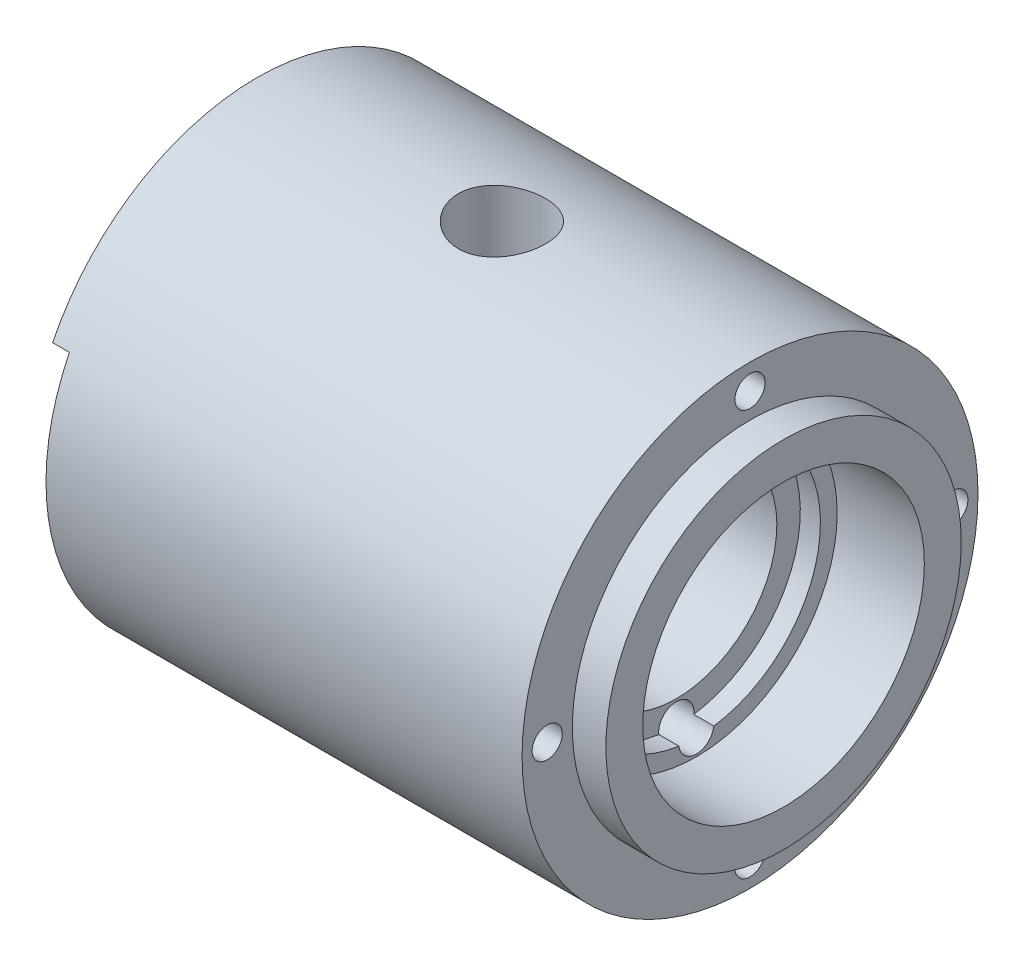
SolidWorks part; units mm, degrees
ref_plane "Front Plane" through (0, 0, 0) normal (0, 0, 1) x (1, 0, 0)
ref_plane "Top Plane" through (0, 0, 0) normal (0, 1, 0) x (1, 0, 0)
ref_plane "Right Plane" through (0, 0, 0) normal (1, 0, 0) x (0, 0, -1)
sketch "Sketch17" plane through (0, 0, 0) normal (0, 0, 1) x (1, 0, 0)
  line L0 (0, 0) -> (156.5215, 0) construction
sketch "Sketch1" plane through (0, 0, 0) normal (1, 0, 0) x (0, 0, -1)
  circle A0 centre (0, 0) radius 68
extrude "Boss-Extrude1" add sketch "Sketch1" along normal blind 157 contours A0
sketch "Sketch2" plane through (0, 0, 0) normal (-1, 0, 0) x (0, 0, 1)
  circle A0 centre (0, 0) radius 26
extrude "Cut-Extrude1" cut sketch "Sketch2" against normal up to next
sketch "Sketch3" plane through (0, 0, 0) normal (-1, 0, 0) x (0, 0, 1)
  line L1 (-68, 30) -> (68, 30)
  line L2 (-68, 30) -> (-68, -68)
  line L3 (-68, -68) -> (68, -68)
  line L4 (68, 30) -> (68, -68)
  circle A2 centre (0, 0) radius 68 construction
  circle A3 centre (0, 0) radius 26 construction
  dimension "D1" = 30
  dimension "D2" = 68
  dimension "D3" = 42
  dimension "D4" = 68
  dimension "D5" = 68
extrude "Cut-Extrude2" cut sketch "Sketch3" against normal blind 5 contours L2 L3 L4 L1
sketch "Sketch4" plane through (5, 0, 0) normal (-1, 0, 0) x (0, 0, 1)
  line L3 (-13.5, 29.0129) -> (13.5, 29.0129)
  arc A3 (-13.5, 29.0129) -> (13.5, 29.0129) centre (0, 0) ccw
  point P2 (-12.1706, 28.9683)
  point P3 (13.4809, 29.0218)
  point P5 (0, 0)
  point P6 (0, 0)
  point P7 (13.5, 28.9963)
  dimension "D1" = 27
extrude "Cut-Extrude3" cut sketch "Sketch4" against normal blind 44
sketch "Sketch7" plane through (157, 0, 0) normal (1, 0, 0) x (0, 0, -1)
  circle A0 centre (0, 0) radius 42
extrude "Cut-Extrude4" cut sketch "Sketch7" against normal blind 26
sketch "Sketch8" plane through (131, 0, 0) normal (1, 0, 0) x (0, 0, -1)
  circle A0 centre (0, 0) radius 37
extrude "Cut-Extrude5" cut sketch "Sketch8" against normal blind 6 contours A0
sketch "Sketch9" plane through (125, 0, 0) normal (1, 0, 0) x (0, 0, -1)
  circle A0 centre (0, 0) radius 30
extrude "Cut-Extrude6" cut sketch "Sketch9" against normal blind 28 contours A0
ref_plane "Plane2" through (0, 0, 68) normal (0, 0, 1) x (1, 0, 0)
sketch "Sketch12" plane through (0, 0, 68) normal (0, 0, 1) x (1, 0, 0)
  line L0 (49, 37.9633) -> (49, -31.4216)
  line L1 (49, -31.4216) -> (59.8739, -42.2955)
  line L2 (59.8739, -42.2955) -> (85.8739, -42.2955)
  line L3 (85.8739, -42.2955) -> (97, -31.1695)
  line L4 (97, -31.1695) -> (97, 37.7112)
  line L5 (97, 37.7112) -> (85.8739, 48.8372)
  line L6 (85.8739, 48.8372) -> (59.8739, 48.8372)
  line L7 (59.8739, 48.8372) -> (49, 37.9633)
  line L8 (157, -68) -> (157, 68) construction
  line L9 (5, 30) -> (5, -68) construction
  dimension "D1" = 60
  dimension "D2" = 44
  dimension "D3" = 26
  dimension "D4" = 26
  dimension "D5" = 135
  dimension "D6" = 135
  dimension "D7" = 135
  dimension "D8" = 135
sketch "Sketch16" plane through (0, 0, 0) normal (-1, 0, 0) x (0, 0, 1)
  line L0 (35.9404, 57.726) -> (61.0246, 30) construction
  line L1 (35.9404, 57.726) -> (0, 68) construction
  arc A0 (61.0246, 30) -> (-61.0246, 30) centre (0, 0) ccw construction
  dimension "D1" = 37.38
  dimension "D2" = 37.3892
ref_plane "Plane5" through (0, 68, 0) normal (0, 1, 0) x (1, 0, 0)
ref_plane "Plane7" through (0, 0, 0) normal (0, 0, 1) x (1, 0, 0)
sketch "Sketch23" plane through (0, 68, 0) normal (0, 1, 0) x (1, 0, 0)
  line L0 (86, -40) -> (86, 40) construction
  point P9 (73, 0)
  dimension "D1" = 13
sketch "Sketch27" plane through (157, 0, 0) normal (1, 0, 0) x (0, 0, -1)
  circle A0 centre (0, 0) radius 68
  circle A1 centre (0, 0) radius 53
  dimension "D1" = 136
  dimension "D2" = 106
extrude "Cut-Extrude9" cut sketch "Sketch27" against normal blind 10
sketch "Sketch36" plane through (0, 0, 0) normal (0, 0, 1) x (1, 0, 0)
  line L0 (49, 29) -> (60, 40)
  line L1 (60, 40) -> (86, 40)
  line L2 (86, 40) -> (97, 29)
  line L8 (147, 68) -> (0, 68) construction
  line L17 (49, 29) -> (49, 0)
  line L18 (0, 0) -> (156.5215, 0) construction
  line L19 (49, 0) -> (97, 0)
  line L20 (97, 0) -> (97, 29)
  line L21 (157, -53) -> (157, 53) construction
  line L22 (5, 30) -> (5, -68) construction
  dimension "D1" = 60
  dimension "D2" = 44
  dimension "D3" = 135
  dimension "D4" = 40
  dimension "D5" = 26
revolve "Cut-Revolve2" cut sketch "Sketch36" angle 360 about L0
hole_wizard "Tap Drill for M1.2x0.25 Tap1" positions "Sketch23" profile "Sketch26" hole size "M1.2x0.25" standard "ISO"
sketch "Sketch26" plane through (73, 68, 0) normal (1, 0, 0) x (0, 0, 1)
  line L0 (0, 0) -> (0, 68)
  line L1 (0, 68) -> (13, 68)
  line L2 (13, 68) -> (13, 0)
  line L5 (13, 0) -> (0, 0)
  line L10 (0, 68) -> (-13, 68) construction
  line L11 (0, -6.35) -> (0, 107.95) construction
  dimension "Hole Dia." = 26
  dimension "Hole Depth" = 68
  dimension "Drill Angle" = 180
sketch "Sketch29" plane through (147, 0, 0) normal (1, 0, 0) x (0, 0, -1)
  line L0 (0, 68) -> (0, 53) construction
  line L1 (53, 0) -> (68, 0) construction
  line L2 (0, -53) -> (0, -68) construction
  line L3 (-53, 0) -> (-68, 0) construction
  line L4 (-68, 74.8) -> (-68, -74.8) construction
  circle A0 centre (0, 0) radius 53 construction
  circle A1 centre (0, 0) radius 53 construction
  circle A2 centre (0, 0) radius 68 construction
  point P21 (0, 60.5)
  point P23 (60.5, 0)
  point P25 (0, -60.5)
  point P27 (-60.5, 0)
hole_wizard "M8 Clearance Hole1" positions "Sketch29" profile "Sketch30" hole size "M8" standard "ISO"
sketch "Sketch30" plane through (147, 0, 60.5) normal (0, 1, 0) x (0, 0, -1)
  line L0 (0, 0) -> (0, 37.7039)
  line L1 (0, 37.7039) -> (4.5, 35)
  line L2 (4.5, 35) -> (4.5, 0)
  line L5 (4.5, 0) -> (0, 0)
  line L10 (0, 37.7039) -> (-4.5, 35) construction
  line L11 (0, -6.35) -> (0, 107.95) construction
  dimension "Hole Dia." = 9
  dimension "Hole Depth" = 35
  dimension "Drill Angle" = 118
ref_plane "Plane4" [suppressed] through (0, 0, 0) normal (0, 0.5285, -0.8489) x (-1, 0, 0)
sketch "Sketch19" [suppressed] plane through (0, 0, 0) normal (0, 0.5285, -0.8489) x (-1, 0, 0)
  line L1 (-97, 30) -> (-97, -30) construction
  line L3 (-27.3689, 310) -> (-67.3689, 310)
  line L9 (0, 0) -> (-156.5215, 0) construction
  line L10 (-67.3689, 310) -> (-95.5, 66.5)
  line L11 (-95.5, 66.5) -> (-50.5, 66.5)
  line L12 (-50.5, 66.5) -> (-27.3689, 310)
  line L13 (0, 68) -> (-147, 68) construction
  dimension "D1" = 310
  dimension "D2" = 83.41
  dimension "D3" = 45
  dimension "D4" = 1.5
  dimension "D5" = 1.5
  dimension "D6" = 40
sketch "Sketch21" [suppressed] plane through (0, 0, 0) normal (0, 0.5285, -0.8489) x (-1, 0, 0)
  line L0 (-67.3689, 310) -> (-69.3689, 310)
  line L1 (-69.3689, 310) -> (-69.3689, 340)
  line L2 (-69.3689, 340) -> (-92.3689, 340)
  line L3 (-92.3689, 340) -> (-92.3689, 350)
  line L4 (-92.3689, 350) -> (-59.3689, 350)
  line L5 (-2.3689, 350) -> (-2.3689, 340)
  line L6 (-2.3689, 340) -> (-25.3689, 340)
  line L7 (-25.3689, 340) -> (-25.3689, 310)
  line L8 (-25.3689, 310) -> (-27.3689, 310)
  line L11 (-59.3689, 350) -> (-59.3689, 320)
  line L12 (-59.3689, 320) -> (-35.3689, 320)
  line L13 (-35.3689, 320) -> (-35.3689, 350)
  line L14 (-35.3689, 350) -> (-2.3689, 350)
  line L15 (-27.3689, 310) -> (-67.3689, 310) construction
  line L17 (-67.3689, 310) -> (-27.3689, 310)
  dimension "D2" = 10
  dimension "D3" = 10
  dimension "D7" = 10
  dimension "D8" = 90
  dimension "D11" = 40
  dimension "D12" = 40
  dimension "D10" = 2
  dimension "D5" = 2
  dimension "D6" = 10
  dimension "D9" = 10
  dimension "D4" = 23
  dimension "D13" = 24
revolve "Revolve1" [suppressed] add sketch "Sketch21" angle 360 about L0
extrude "Boss-Extrude4" [suppressed] add sketch "Sketch19" along normal mid plane 10
pattern_circular "CirPattern4" [suppressed] count 4 every 90 about axis through (0, 0, 0) along (1, 0, 0) of bodies 117
sketch "Esquisse4" plane through (131, 0, 0) normal (1, 0, 0) x (0, 0, -1)
  line L0 (0, 0) -> (0, -36) construction
  point P11 (0, -36)
  dimension "D1" = 36
  dimension "D2" = 0
hole_wizard "M10 Clearance Hole1" positions "Esquisse4" profile "Esquisse6" hole size "M10" standard "ANSI Metric"
sketch "Esquisse6" plane through (131, -36, 0) normal (0, 1, 0) x (0, 0, -1)
  line L0 (0, 0) -> (0, 15)
  line L1 (0, 15) -> (5.25, 15)
  line L2 (5.25, 15) -> (5.25, 0)
  line L5 (5.25, 0) -> (0, 0)
  line L10 (0, 15) -> (-5.25, 15) construction
  line L11 (0, -6.35) -> (0, 107.95) construction
  dimension "Hole Dia." = 10.5
  dimension "Hole Depth" = 15
  dimension "Drill Angle" = 180
equation "\"D1@Sketch3\"=26+8/2"
equation "\"D2@Sketch3\"=26+\"D3@Sketch3\""
equation "\"D4@Sketch3\"=\"D2@Sketch3\""
equation "\"D5@Sketch3\"=\"D2@Sketch3\""
equation "\"D12@Sketch21\"=\"D11@Sketch21\""
equation "\"D2@Sketch27\"=\"D1@Sketch27\"-15*2"
equation "\"D4@Sketch21\"=(\"D8@Sketch21\"-\"D6@Sketch21\"-\"D13@Sketch21\"-\"D9@Sketch21\")/2"
